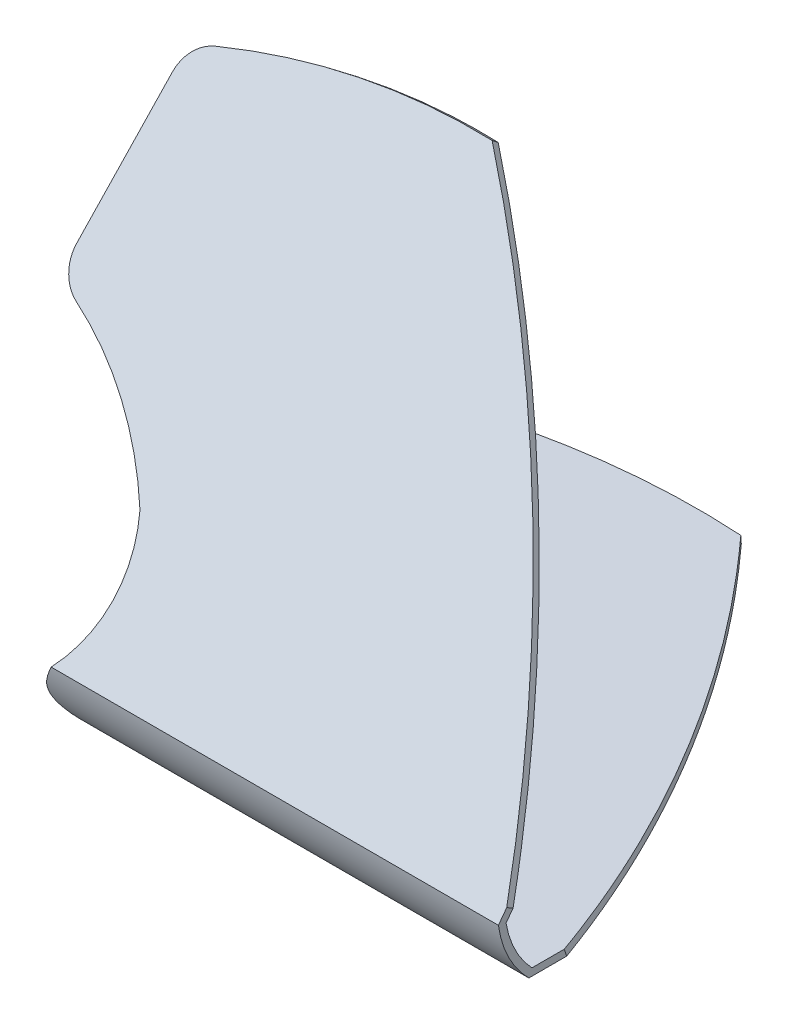
SolidWorks part; units mm, degrees
material "Corrugated Paper"
ref_plane "Front Plane" through (0, 0, 0) normal (0, 0, 1) x (1, 0, 0)
ref_plane "Top Plane" through (0, 0, 0) normal (0, 1, 0) x (1, 0, 0)
ref_plane "Right Plane" through (0, 0, 0) normal (1, 0, 0) x (0, 0, -1)
sketch "Sketch2" plane through (0, 0, 0) normal (0, 1, 0) x (1, 0, 0)
  line L0 (55.428, -792.898) -> (95.428, -792.898) construction
  line L1 (83.6142, 6.6908) -> (143.6142, 6.6908)
  dimension "D1" = 60
sketch "Sketch3" plane through (0, 0, 0) normal (0, 1, 0) x (1, 0, 0)
  line L0 (142.4391, 11.9148) -> (143.6142, 6.6908)
  line L2 (83.6142, 6.6908) -> (143.6142, 6.6908) construction
  line L3 (83.6142, 6.6908) -> (143.6142, 6.6908)
  line L4 (83.6142, 6.6908) -> (68.6142, 6.6908)
  line L5 (191.7256, 88.676) -> (191.7256, 105.6462)
  line L7 (190.2906, 113.1536) -> (190.6216, 112.1991)
  arc A3 (15.8669, 117.6272) -> (179.0708, 125.0688) centre (105.3829, -52.2171) cw
  arc A4 (191.7256, 88.676) -> (185.7403, 61.0245) centre (134.7126, 86.5432) cw
  arc A5 (142.4391, 11.9148) -> (185.7403, 61.0245) centre (71.3762, 118.2174) ccw
  arc A8 (68.6142, 6.6908) -> (71.7792, 42.1924) centre (41.0768, 27.0377) ccw
  arc A9 (71.7792, 42.1924) -> (24.9056, 75.5028) centre (4.1864, -3.2878) ccw
  arc A10 (24.9056, 75.5028) -> (5.2478, 98.44) centre (30.682, 100.3455) cw
  arc A11 (179.0708, 125.0688) -> (190.2906, 113.1536) centre (171.3946, 106.6006) cw
  arc A12 (191.7256, 105.6462) -> (190.6216, 112.1991) centre (171.7256, 105.6462) ccw
  arc A13 (15.8669, 117.6272) -> (5.2478, 98.44) centre (25.192, 99.9342) ccw
  point P8 (142.4391, 11.9148)
  dimension "D1" = 20
  dimension "D2" = 20
  dimension "D3" = 20
sketch "Sketch6" plane through (0, 0, 0) normal (0, 1, 0) x (1, 0, 0)
  line L0 (176.7256, 81.1411) -> (132.9611, 26.509) construction
  line L1 (83.6142, 6.6908) -> (143.6142, 6.6908) construction
  line L3 (83.6142, 6.6908) -> (83.6142, 46.6908) construction
  line L4 (176.7256, 88.3742) -> (176.7256, 105.6462)
  line L5 (176.7256, 88.3742) -> (176.7256, 105.6462)
  line L6 (83.6142, 6.6908) -> (143.6142, 6.6908) construction
  line L7 (33.3185, 145.5682) -> (33.3185, 97.0828) construction
  line L8 (33.3185, 121.3255) -> (83.6142, 46.6908) construction
  line L9 (176.7256, 81.1411) -> (133.3109, 122.5557) construction
  line L10 (133.3109, 122.5557) -> (33.3185, 121.3255) construction
  line L11 (143.6142, 6.6908) -> (122.3079, 46.3272)
  arc A0 (84.7538, 49.7708) -> (83.6142, 6.6908) centre (53.2872, 29.0481) cw
  arc A1 (173.3136, 111.2177) -> (176.7256, 105.6462) centre (170.5894, 105.7189) cw
  arc A77 (176.1186, 108.2388) -> (173.3136, 111.2177) centre (171.3946, 106.6006) ccw
  arc A78 (173.3136, 111.2177) -> (22.8607, 104.3575) centre (105.3829, -52.2171) ccw
  arc A79 (22.8607, 104.3575) -> (20.2059, 99.5607) centre (25.192, 99.9342) ccw
  arc A80 (20.2059, 99.5607) -> (28.4585, 90.0781) centre (30.682, 100.3455) ccw
  arc A81 (84.7538, 49.7708) -> (28.4585, 90.0781) centre (4.1864, -3.2878) ccw
  arc A82 (80.6783, -2.2231) -> (84.7538, 49.7708) centre (41.0768, 27.0377) ccw
  arc A84 (173.3136, 111.2177) -> (22.8607, 104.3575) centre (105.3829, -52.2171) ccw
  arc A85 (22.8607, 104.3575) -> (20.2059, 99.5607) centre (25.192, 99.9342) ccw
  arc A86 (20.2059, 99.5607) -> (28.4585, 90.0781) centre (30.682, 100.3455) ccw
  arc A87 (84.7538, 49.7708) -> (28.4585, 90.0781) centre (4.1864, -3.2878) ccw
  arc A93 (176.7256, 105.6462) -> (176.4496, 107.2844) centre (171.7256, 105.6462) ccw
  arc A94 (172.3244, 67.7337) -> (176.7256, 88.3742) centre (134.7126, 86.5432) ccw
  arc A95 (134.1028, 24.385) -> (172.3244, 67.7337) centre (71.3762, 118.2174) ccw
  arc A97 (172.3244, 67.7337) -> (176.7256, 88.3742) centre (134.7126, 86.5432) ccw
  arc A98 (134.1028, 24.385) -> (172.3244, 67.7337) centre (71.3762, 118.2174) ccw
  dimension "D3" = 40
  dimension "D4" = 60
  dimension "D5" = 100
  dimension "D6" = 90
  dimension "D7" = 45
  dimension "D8" = 70
  dimension "D9" = 60
  dimension "D1" = 15
  dimension "D2" = 15
sketch "Sketch9" plane through (0, 0, 0) normal (1, 0, 0) x (0, 0, -1)
  line L1 (42.1924, 0) -> (6.6908, 0) construction
  line L3 (42.1924, 0) -> (6.6908, 0) construction
  arc A0 (6.6908, 0) -> (-1.6966, 16.7647) centre (-14.2573, 0) ccw
  point P3 (-7.9134, 22.1181)
  point P4 (0, 0)
  point P7 (-14.2573, 19.833)
  point P8 (0, 0)
  point P9 (6.6908, 0)
  point P10 (-3.8532, 18.4411)
  point P11 (6.6908, 0)
  point P14 (0, 15.0387)
  point P15 (-2.2442, 16.0339)
  point P16 (0, 0)
  point P17 (0, 0)
sweep "Sweep1" add profiles "Sketch3" path "Sketch9"
ref_plane "Plane1" through (191.7256, 0, 0) normal (1, 0, 0) x (0, 0, -1)
sketch "Sketch11" plane through (191.7256, 0, 0) normal (1, 0, 0) x (0, 0, -1)
  line L0 (47.4624, 82.3769) -> (30.8823, 60.2476) construction
  line L1 (30.8823, 60.2476) -> (1.4357, 20.9454) construction
  line L2 (61.0245, 0) -> (88.676, 0) construction
  line L3 (11.9148, 0) -> (61.0245, 0) construction
  line L4 (47.4624, 82.3769) -> (30.8823, 60.2476)
  line L5 (30.8823, 60.2476) -> (1.4357, 20.9454)
  line L6 (61.0245, 0) -> (88.676, 0)
  line L7 (11.9148, 0) -> (61.0245, 0)
  arc A0 (88.676, 0) -> (47.4624, 82.3769) centre (-14.2573, 0) ccw construction
  arc A1 (88.676, 0) -> (47.4624, 82.3769) centre (-14.2573, 0) ccw
  arc A2 (11.9148, 0) -> (1.4357, 20.9454) centre (-14.2573, 0) ccw construction
  arc A3 (11.9148, 0) -> (1.4357, 20.9454) centre (-14.2573, 0) ccw
extrude "Boss-Extrude5" add sketch "Sketch11" against normal up to surface (60.3337 mm away) up to face at (143.0267, 9.9845, -5.6996)
sketch "Sketch12" plane through (191.7256, 0, 0) normal (1, 0, 0) x (0, 0, -1)
  line L0 (1.4357, 20.9454) -> (-1.6966, 16.7647)
  line L1 (6.6908, 0) -> (11.9148, 0)
  arc A0 (-1.6966, 16.7647) -> (6.6908, 0) centre (27.3178, 20.8002) ccw
  arc A1 (11.9148, 0) -> (1.4357, 20.9454) centre (-14.2573, 0) ccw construction
  arc A2 (11.9148, 0) -> (1.4357, 20.9454) centre (-14.2573, 0) ccw
extrude "Boss-Extrude6" add sketch "Sketch12" against normal up to surface (119.9306 mm away) up to face at (72.6886, 16.3113, -18.3454)
sketch "Sketch14" plane through (191.7256, 0, 0) normal (1, 0, 0) x (0, 0, -1)
  line L38 (105.6462, 2) -> (149.6835, 2)
  line L39 (149.6835, 2) -> (149.6835, 144.6644)
  line L40 (149.6835, 144.6644) -> (96.6295, 144.6644)
  line L41 (46.5052, 77.7639) -> (96.6295, 144.6644)
  line L42 (88.676, 2) -> (105.6462, 2)
  line L43 (84.4104, 2) -> (88.676, 2)
  line L44 (7.5315, 2) -> (84.4104, 2)
  line L45 (46.5052, 77.7639) -> (0.408, 16.2382)
  line L46 (88.676, 2) -> (105.6462, 2)
  line L47 (84.4104, 2) -> (88.676, 2)
  line L48 (7.5315, 2) -> (84.4104, 2)
  line L49 (46.5052, 77.7639) -> (0.408, 16.2382)
  line L50 (69.2838, 111.5018) -> (62.1393, 101.9661) construction
  arc A14 (0.408, 16.2382) -> (7.5315, 2) centre (27.3178, 20.8002) ccw
  arc A15 (0.408, 16.2382) -> (7.5315, 2) centre (27.3178, 20.8002) ccw
  point P3 (46.5052, 157.0119)
  point P4 (100.9221, 141.222)
  dimension "D1" = 2
extrude "Cut-Extrude2" cut sketch "Sketch14" against normal through all both and the other way through all
ref_axis "Axis1" through (64.3378, 20.8002, -27.3178) along (1, 0, 0)
ref_axis "Axis2" through (-4.1367, 0, 0) along (1, 0, 0)
ref_plane "Plane2" through (0, 0, 0) normal (0, -0.1018, 0.9948) x (1, 0, 0)
sketch "Sketch15" plane through (0, 0, 0) normal (0, -0.1018, 0.9948) x (1, 0, 0)
  line L0 (64.3378, 17.9106) -> (191.7256, 17.9106) construction
  line L1 (24.6487, -86.425) -> (-27.204, -86.425)
  line L2 (24.6487, -86.425) -> (24.6487, 122.2462)
  line L3 (24.6487, 122.2462) -> (-27.204, 122.2462)
  line L4 (-27.204, -86.425) -> (-27.204, 122.2462)
  line L5 (24.6487, -86.425) -> (-27.204, 122.2462) construction
  line L6 (24.6487, 122.2462) -> (-27.204, -86.425) construction
  point P0 (-1.2777, 17.9106)
  point P7 (-27.204, 116.3249)
extrude "Cut-Extrude3" cut sketch "Sketch15" against normal through all draft 7 draft outward yes
fillet "Fillet1" radius 10 4 edges
sketch "Sketch16" plane through (0, 6.8415, 9.1314) normal (0, 0.5996, 0.8003) x (1, 0, 0)
  line L0 (95.6836, 159.6878) -> (195.0908, 159.6878)
  line L1 (195.0908, 159.6878) -> (195.0908, 6.8034)
  arc A0 (195.0908, 6.8034) -> (95.6836, 159.6878) centre (-158.6069, -114.4148) ccw
  point P4 (195.4821, 10.5719)
  point P5 (195.0908, 6.8034)
sketch "Sketch17" plane through (0, 0, 0) normal (1, 0, 0) x (0, 0, -1)
  line L0 (86.6188, 134.6387) -> (-5.052, 12.2863) construction
  arc A0 (62.3709, 102.2752) -> (121.2683, -10.2107) centre (-14.786, -9.7862) cw
sweep "Cut-Sweep1" cut profiles "Sketch16" path "Sketch17"
